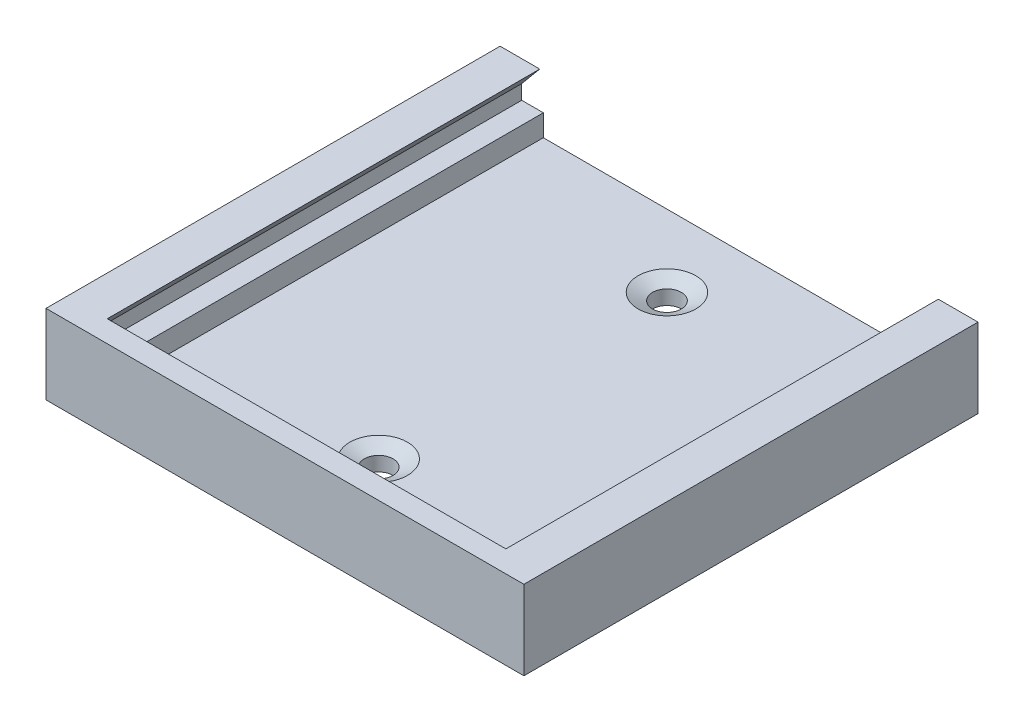
SolidWorks part; units mm, degrees
ref_plane "Спереди" through (0, 0, 0) normal (0, 0, 1) x (1, 0, 0)
ref_plane "Сверху" through (0, 0, 0) normal (0, 1, 0) x (1, 0, 0)
ref_plane "Справа" through (0, 0, 0) normal (1, 0, 0) x (0, 0, -1)
sketch "Эскиз1" plane through (0, 0, 0) normal (0, 0, 1) x (1, 0, 0)
  line L1 (0, 0) -> (66.3, 0)
  line L2 (0, 0) -> (0, 3)
  line L3 (0, 3) -> (66.3, 3)
  line L4 (66.3, 0) -> (66.3, 3)
  dimension "D1" = 66.3
  dimension "D2" = 3
extrude "base" add sketch "Эскиз1" along normal blind 60
sketch "Эскиз2" plane through (0, 0, 0) normal (0, 0, 1) x (1, 0, 0)
  line L0 (66.3, 3) -> (0, 3) construction
  line L1 (0, 3) -> (6, 3)
  line L2 (0, 3) -> (0, 11)
  line L3 (0, 11) -> (5.5, 11)
  line L4 (60.3, 6) -> (60.3, 3)
  line L5 (3, 6) -> (3, 8)
  line L6 (3, 8) -> (5.5, 11)
  line L7 (33.15, 3) -> (33.15, 0) construction
  line L8 (0, 0) -> (66.3, 0) construction
  line L9 (63.3, 6) -> (60.3, 6)
  line L10 (63.3, 8) -> (60.8, 11)
  line L11 (63.3, 6) -> (63.3, 8)
  line L12 (66.3, 11) -> (60.8, 11)
  line L13 (66.3, 3) -> (66.3, 11)
  line L14 (66.3, 3) -> (60.3, 3)
  line L15 (3, 6) -> (6, 6)
  line L16 (6, 6) -> (6, 3)
  dimension "D1" = 5.5
  dimension "D2" = 8
  dimension "D3" = 2
  dimension "D4" = 6
  dimension "D5" = 3
  dimension "D6" = 3
extrude "rails" add sketch "Эскиз2" along normal up to surface (60 mm away) up to face at (33.15, 1.5, 60)
sketch "Эскиз3" plane through (0, 3, 0) normal (0, 1, 0) x (1, 0, 0)
  line L0 (33.15, 0) -> (33.15, -60) construction
  line L1 (60.3, 0) -> (6, 0) construction
  line L2 (60.3, -60) -> (6, -60) construction
  circle A0 centre (33.15, -10) radius 2
  circle A1 centre (33.15, -50) radius 2
  dimension "D3" = 4
  dimension "D1" = 10
  dimension "D2" = 10
extrude "holes" cut sketch "Эскиз3" against normal through all
chamfer "Фаска1" distance 2 distance2 1 2 edges at (33.15, 3, 12) (33.15, 3, 52) first distance on face at (33.15, 3, 52)
sketch "Эскиз4" plane through (0, 0, 60) normal (0, 0, 1) x (1, 0, 0)
  line L1 (0, 11) -> (66.3, 11)
  line L2 (0, 11) -> (0, 0)
  line L3 (0, 0) -> (66.3, 0)
  line L4 (66.3, 11) -> (66.3, 0)
extrude "floor" add sketch "Эскиз4" along normal blind 3
